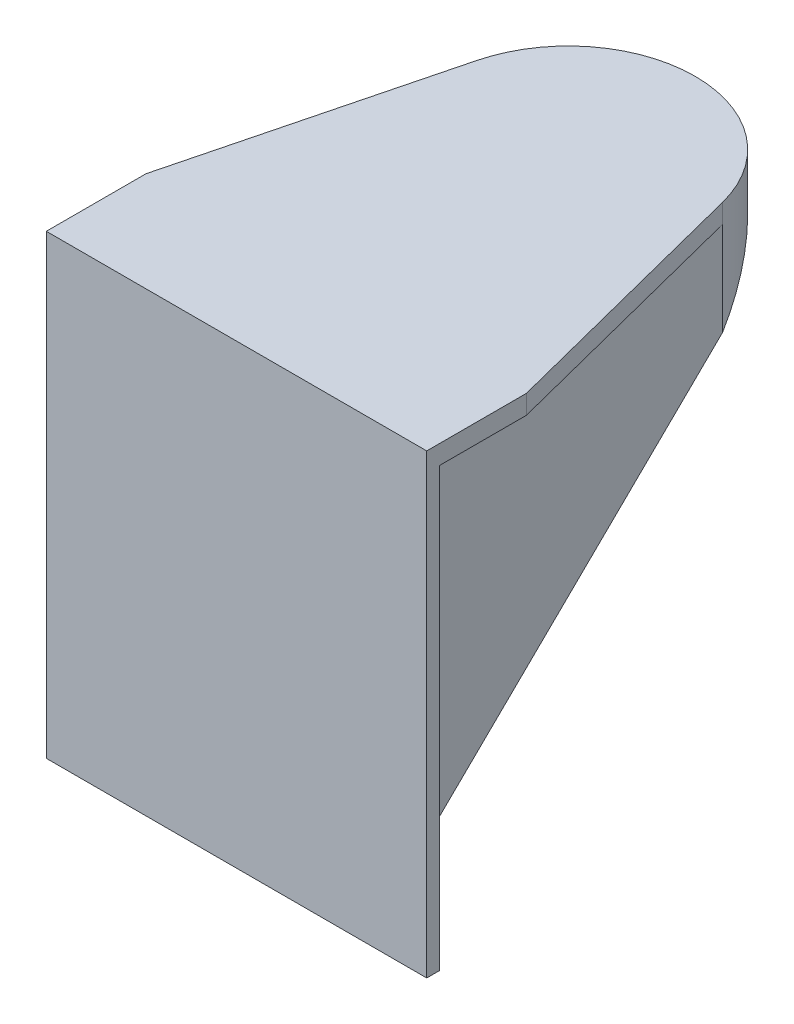
SolidWorks part; units mm, degrees
ref_plane "Front Plane" through (0, 0, 0) normal (0, 0, 1) x (1, 0, 0)
ref_plane "Top Plane" through (0, 0, 0) normal (0, 1, 0) x (1, 0, 0)
ref_plane "Right Plane" through (0, 0, 0) normal (1, 0, 0) x (0, 0, -1)
sketch "Sketch1" plane through (0, 0, 0) normal (0, 1, 0) x (1, 0, 0)
  line L0 (-30, -18) -> (30, -18) construction
  line L1 (-30, 10) -> (-22.5, 10) construction
  line L2 (-46.46, 5.4904) -> (-53.96, -7.5) construction
  line L3 (-30, -10) -> (-22.5, -10) construction
  line L4 (30, 10) -> (30, 2.5) construction
  line L5 (0, 0) -> (0, -75.5561) construction
  line L6 (38.6603, -23) -> (51.362, -45) construction
  line L7 (55.7735, -52.641) -> (58.3716, -51.141) construction
  line L8 (59.1036, -48.409) -> (41.8357, -18.5) construction
  line L9 (43.1036, -13.7679) -> (55.6921, -6.5) construction
  line L10 (56.4241, -3.7679) -> (51.362, 5) construction
  line L11 (25.3812, 20) -> (-25.3812, 20) construction
  line L12 (43.5677, -13.5) -> (36.0677, -0.5096) construction
  line L13 (36.0677, -0.5096) -> (46.46, 5.4904) construction
  line L14 (46.46, 5.4904) -> (53.96, -7.5) construction
  line L15 (-36.0677, -0.5096) -> (-46.46, 5.4904) construction
  line L16 (-43.5677, -13.5) -> (-36.0677, -0.5096) construction
  line L17 (-56.4241, -3.7679) -> (-51.362, 5) construction
  line L18 (-43.1036, -13.7679) -> (-55.6921, -6.5) construction
  line L19 (-59.1036, -48.409) -> (-41.8357, -18.5) construction
  line L20 (-55.7735, -52.641) -> (-58.3716, -51.141) construction
  line L21 (-38.6603, -23) -> (-51.362, -45) construction
  line L22 (-30, 10) -> (-30, 2.5) construction
  line L23 (30, 2.5) -> (25, 2.5) construction
  line L24 (25, 2.5) -> (25, -2.5) construction
  line L25 (25, -2.5) -> (30, -2.5) construction
  line L26 (30, -2.5) -> (30, -10) construction
  line L27 (22.5, -10) -> (22.5, -5) construction
  line L28 (22.5, -5) -> (17.5, -5) construction
  line L29 (17.5, -5) -> (17.5, -10) construction
  line L30 (22.5, -10) -> (30, -10) construction
  line L31 (17.5, 10) -> (17.5, 9) construction
  line L32 (17.5, 9) -> (22.5, 9) construction
  line L33 (22.5, 9) -> (22.5, 10) construction
  line L34 (22.5, 10) -> (30, 10) construction
  line L35 (2.5, -10) -> (2.5, -5) construction
  line L36 (2.5, -5) -> (-2.5, -5) construction
  line L37 (-2.5, -5) -> (-2.5, -10) construction
  line L38 (-2.5, 10) -> (-2.5, 9) construction
  line L39 (-2.5, 9) -> (2.5, 9) construction
  line L40 (2.5, 9) -> (2.5, 10) construction
  line L41 (-17.5, -10) -> (-17.5, -5) construction
  line L42 (-17.5, -5) -> (-22.5, -5) construction
  line L43 (-22.5, -5) -> (-22.5, -10) construction
  line L44 (-22.5, 10) -> (-22.5, 9) construction
  line L45 (-22.5, 9) -> (-17.5, 9) construction
  line L46 (-17.5, 9) -> (-17.5, 10) construction
  line L47 (-17.5, 10) -> (-2.5, 10) construction
  line L48 (-17.5, -10) -> (-2.5, -10) construction
  line L49 (2.5, -10) -> (17.5, -10) construction
  line L50 (2.5, 10) -> (17.5, 10) construction
  line L51 (-25, -2.5) -> (-30, -2.5) construction
  line L52 (-25, 2.5) -> (-25, -2.5) construction
  line L53 (-30, 2.5) -> (-25, 2.5) construction
  line L54 (-30, -2.5) -> (-30, -10) construction
  line L55 (-54.8261, -52) -> (54.8261, -52) construction
  line L56 (-49.6299, -48) -> (49.6299, -48) construction
  line L57 (-55.6921, -52.5) -> (-55.7735, -52.641) construction
  line L58 (55.6921, -52.5) -> (55.7735, -52.641) construction
  line L59 (207.8868, -326.1089) -> (177.8868, -378.0704) construction
  line L60 (232.1355, -340.1089) -> (228.3855, -346.6041) construction
  line L61 (214.815, -330.1089) -> (211.065, -336.6041) construction
  line L62 (202.1355, -392.0704) -> (195.6403, -388.3204) construction
  line L63 (169.2265, -383.0704) -> (143.8231, -383.0704) construction
  line L64 (135, -383.0704) -> (135, -386.0704) construction
  line L65 (137, -388.0704) -> (171.5359, -388.0704) construction
  line L66 (175, -391.5345) -> (175, -406.0704) construction
  line L67 (177, -408.0704) -> (187.1244, -408.0704) construction
  line L68 (213.1051, -393.0704) -> (238.4863, -349.1089) construction
  line L69 (233.4241, -310.3409) -> (238.4863, -319.1089) construction
  line L70 (218.1036, -316.8768) -> (230.6921, -309.6089) construction
  line L71 (196.1036, -285.6999) -> (213.3716, -315.6089) construction
  line L72 (190.7735, -286.4679) -> (193.3716, -284.9679) construction
  line L73 (207.8868, -316.1089) -> (195.185, -294.1089) construction
  line L74 (232.1355, -340.1089) -> (225.6403, -336.3589) construction
  line L75 (195.6403, -388.3204) -> (198.1403, -383.9903) construction
  line L76 (198.1403, -383.9903) -> (193.8101, -381.4903) construction
  line L77 (193.8101, -381.4903) -> (191.3101, -385.8204) construction
  line L78 (191.3101, -385.8204) -> (184.815, -382.0704) construction
  line L79 (188.565, -375.5752) -> (192.8951, -378.0752) construction
  line L80 (192.8951, -378.0752) -> (195.3951, -373.7451) construction
  line L81 (195.3951, -373.7451) -> (191.065, -371.2451) construction
  line L82 (188.565, -375.5752) -> (184.815, -382.0704) construction
  line L83 (208.3855, -381.2451) -> (207.5194, -380.7451) construction
  line L84 (207.5194, -380.7451) -> (205.0194, -385.0752) construction
  line L85 (205.0194, -385.0752) -> (205.8855, -385.5752) construction
  line L86 (205.8855, -385.5752) -> (202.1355, -392.0704) construction
  line L87 (198.565, -358.2547) -> (202.8951, -360.7547) construction
  line L88 (202.8951, -360.7547) -> (205.3951, -356.4246) construction
  line L89 (205.3951, -356.4246) -> (201.065, -353.9246) construction
  line L90 (218.3855, -363.9246) -> (217.5194, -363.4246) construction
  line L91 (217.5194, -363.4246) -> (215.0194, -367.7547) construction
  line L92 (215.0194, -367.7547) -> (215.8855, -368.2547) construction
  line L93 (208.565, -340.9342) -> (212.8951, -343.4342) construction
  line L94 (212.8951, -343.4342) -> (215.3951, -339.1041) construction
  line L95 (215.3951, -339.1041) -> (211.065, -336.6041) construction
  line L96 (228.3855, -346.6041) -> (227.5194, -346.1041) construction
  line L97 (227.5194, -346.1041) -> (225.0194, -350.4342) construction
  line L98 (225.0194, -350.4342) -> (225.8855, -350.9342) construction
  line L99 (225.8855, -350.9342) -> (218.3855, -363.9246) construction
  line L100 (208.565, -340.9342) -> (201.065, -353.9246) construction
  line L101 (198.565, -358.2547) -> (191.065, -371.2451) construction
  line L102 (215.8855, -368.2547) -> (208.3855, -381.2451) construction
  line L103 (218.8101, -338.189) -> (221.3101, -333.8589) construction
  line L104 (223.1403, -340.689) -> (218.8101, -338.189) construction
  line L105 (225.6403, -336.3589) -> (223.1403, -340.689) construction
  line L106 (221.3101, -333.8589) -> (214.815, -330.1089) construction
  line L107 (190.8549, -287.6089) -> (136.0289, -382.5704) construction
  line L108 (191.7209, -294.1089) -> (142.091, -380.0704) construction
  line L109 (190.8549, -286.6089) -> (190.7735, -286.4679) construction
  line L110 (135.1628, -383.0704) -> (135, -383.0704) construction
  line L111 (236.46, -323.5993) -> (228.96, -310.6089) construction
  line L112 (175, -392.0704) -> (190, -392.0704) construction
  line L113 (190, -392.0704) -> (190, -404.0704) construction
  line L114 (190, -404.0704) -> (175, -404.0704) construction
  line L115 (226.0677, -329.5993) -> (236.46, -323.5993) construction
  line L116 (218.5677, -316.6089) -> (226.0677, -329.5993) construction
  line L117 (-177.8868, -378.0704) -> (-207.8868, -326.1089) construction
  line L118 (-202.1355, -392.0704) -> (-205.8855, -385.5752) construction
  line L119 (-184.815, -382.0704) -> (-188.565, -375.5752) construction
  line L120 (-232.1355, -340.1089) -> (-225.6403, -336.3589) construction
  line L121 (-207.8868, -316.1089) -> (-195.185, -294.1089) construction
  line L122 (-190.7735, -286.4679) -> (-193.3716, -284.9679) construction
  line L123 (-196.1036, -285.6999) -> (-213.3716, -315.6089) construction
  line L124 (-218.1036, -316.8768) -> (-230.6921, -309.6089) construction
  line L125 (-233.4241, -310.3409) -> (-238.4863, -319.1089) construction
  line L126 (-238.4863, -349.1089) -> (-213.1051, -393.0704) construction
  line L127 (-177, -408.0704) -> (-187.1244, -408.0704) construction
  line L128 (-175, -391.5345) -> (-175, -406.0704) construction
  line L129 (-137, -388.0704) -> (-171.5359, -388.0704) construction
  line L130 (-135, -383.0704) -> (-135, -386.0704) construction
  line L131 (-169.2265, -383.0704) -> (-143.8231, -383.0704) construction
  line L132 (-202.1355, -392.0704) -> (-195.6403, -388.3204) construction
  line L133 (-225.6403, -336.3589) -> (-223.1403, -340.689) construction
  line L134 (-223.1403, -340.689) -> (-218.8101, -338.189) construction
  line L135 (-218.8101, -338.189) -> (-221.3101, -333.8589) construction
  line L136 (-221.3101, -333.8589) -> (-214.815, -330.1089) construction
  line L137 (-211.065, -336.6041) -> (-215.3951, -339.1041) construction
  line L138 (-215.3951, -339.1041) -> (-212.8951, -343.4342) construction
  line L139 (-212.8951, -343.4342) -> (-208.565, -340.9342) construction
  line L140 (-211.065, -336.6041) -> (-214.815, -330.1089) construction
  line L141 (-225.8855, -350.9342) -> (-225.0194, -350.4342) construction
  line L142 (-225.0194, -350.4342) -> (-227.5194, -346.1041) construction
  line L143 (-227.5194, -346.1041) -> (-228.3855, -346.6041) construction
  line L144 (-228.3855, -346.6041) -> (-232.1355, -340.1089) construction
  line L145 (-201.065, -353.9246) -> (-205.3951, -356.4246) construction
  line L146 (-205.3951, -356.4246) -> (-202.8951, -360.7547) construction
  line L147 (-202.8951, -360.7547) -> (-198.565, -358.2547) construction
  line L148 (-215.8855, -368.2547) -> (-215.0194, -367.7547) construction
  line L149 (-215.0194, -367.7547) -> (-217.5194, -363.4246) construction
  line L150 (-217.5194, -363.4246) -> (-218.3855, -363.9246) construction
  line L151 (-191.065, -371.2451) -> (-195.3951, -373.7451) construction
  line L152 (-195.3951, -373.7451) -> (-192.8951, -378.0752) construction
  line L153 (-192.8951, -378.0752) -> (-188.565, -375.5752) construction
  line L154 (-205.8855, -385.5752) -> (-205.0194, -385.0752) construction
  line L155 (-205.0194, -385.0752) -> (-207.5194, -380.7451) construction
  line L156 (-207.5194, -380.7451) -> (-208.3855, -381.2451) construction
  line L157 (-208.3855, -381.2451) -> (-215.8855, -368.2547) construction
  line L158 (-191.065, -371.2451) -> (-198.565, -358.2547) construction
  line L159 (-201.065, -353.9246) -> (-208.565, -340.9342) construction
  line L160 (-218.3855, -363.9246) -> (-225.8855, -350.9342) construction
  line L161 (-193.8101, -381.4903) -> (-191.3101, -385.8204) construction
  line L162 (-198.1403, -383.9903) -> (-193.8101, -381.4903) construction
  line L163 (-195.6403, -388.3204) -> (-198.1403, -383.9903) construction
  line L164 (-191.3101, -385.8204) -> (-184.815, -382.0704) construction
  line L165 (-136.0289, -382.5704) -> (-190.8549, -287.6089) construction
  line L166 (-142.091, -380.0704) -> (-191.7209, -294.1089) construction
  line L167 (-135.1628, -383.0704) -> (-135, -383.0704) construction
  line L168 (-190.8549, -286.6089) -> (-190.7735, -286.4679) construction
  line L169 (-190, -404.0704) -> (-175, -404.0704) construction
  line L170 (-218.5677, -316.6089) -> (-226.0677, -329.5993) construction
  line L171 (-226.0677, -329.5993) -> (-236.46, -323.5993) construction
  line L172 (-236.46, -323.5993) -> (-228.96, -310.6089) construction
  line L173 (-190, -392.0704) -> (-190, -404.0704) construction
  line L174 (-175, -392.0704) -> (-190, -392.0704) construction
  line L175 (-132.8534, -388.0704) -> (132.8534, -388.0704) construction
  line L176 (-132.8534, -388.0704) -> (-194.0303, -282.1089) construction
  line L177 (-194.0303, -282.1089) -> (-61.1769, -52) construction
  line L178 (-61.1769, -52) -> (61.1769, -52) construction
  line L179 (61.1769, -52) -> (194.0303, -282.1089) construction
  line L180 (-30, -408.0704) -> (30, -408.0704)
  line L181 (132.8534, -388.0704) -> (194.0303, -282.1089) construction
  line L182 (30, -372.3509) -> (30, -408.0704)
  line L183 (-30, -372.3509) -> (-30, -408.0704)
  line L184 (-21, -395.2107) -> (-21, -385.2107)
  line L185 (-25, -385.2107) -> (-25, -395.2107)
  line L186 (-30, -390.2107) -> (-25, -390.2107) construction
  line L187 (25, -385.2107) -> (25, -395.2107)
  line L188 (21, -395.2107) -> (21, -385.2107)
  circle A0 centre (0, 0) radius 31.6228 construction
  arc A1 (30, -18) -> (38.6603, -23) centre (30, -28) cw construction
  arc A2 (51.362, 5) -> (25.3812, 20) centre (25.3812, -10) ccw construction
  arc A3 (41.1036, -13.7679) -> (40.1036, -17.5) centre (40.1036, -15.5) ccw construction
  arc A4 (58.3716, -51.141) -> (59.1036, -48.409) centre (57.3716, -49.409) ccw construction
  arc A5 (55.6921, -6.5) -> (56.4241, -3.7679) centre (54.6921, -4.7679) ccw construction
  arc A6 (40.1036, -17.5) -> (41.8357, -18.5) centre (40.1036, -19.5) cw construction
  arc A7 (41.1036, -13.7679) -> (43.1036, -13.7679) centre (42.1036, -12.0359) ccw construction
  arc A8 (-41.1036, -13.7679) -> (-43.1036, -13.7679) centre (-42.1036, -12.0359) cw construction
  arc A9 (-40.1036, -17.5) -> (-41.8357, -18.5) centre (-40.1036, -19.5) ccw construction
  arc A10 (-55.6921, -6.5) -> (-56.4241, -3.7679) centre (-54.6921, -4.7679) cw construction
  arc A11 (-58.3716, -51.141) -> (-59.1036, -48.409) centre (-57.3716, -49.409) cw construction
  arc A12 (-41.1036, -13.7679) -> (-40.1036, -17.5) centre (-40.1036, -15.5) cw construction
  arc A13 (-51.362, 5) -> (-25.3812, 20) centre (-25.3812, -10) cw construction
  arc A14 (-30, -18) -> (-38.6603, -23) centre (-30, -28) ccw construction
  arc A15 (55.6921, -52.5) -> (54.8261, -52) centre (54.8261, -53) ccw construction
  arc A16 (-54.8261, -52) -> (-55.6921, -52.5) centre (-54.8261, -53) ccw construction
  arc A17 (49.6299, -48) -> (51.362, -45) centre (49.6299, -46) ccw construction
  arc A18 (-49.6299, -48) -> (-51.362, -45) centre (-49.6299, -46) cw construction
  circle A19 centre (0, -240.7264) radius 147.344 construction
  arc A20 (177.8868, -378.0704) -> (169.2265, -383.0704) centre (169.2265, -373.0704) cw construction
  arc A21 (187.1244, -408.0704) -> (213.1051, -393.0704) centre (187.1244, -378.0704) ccw construction
  arc A22 (176, -389.8025) -> (173.2679, -387.0704) centre (175, -388.0704) ccw construction
  arc A23 (135, -386.0704) -> (137, -388.0704) centre (137, -386.0704) ccw construction
  arc A24 (175, -406.0704) -> (177, -408.0704) centre (177, -406.0704) ccw construction
  arc A25 (173.2679, -387.0704) -> (171.5359, -388.0704) centre (171.5359, -386.0704) cw construction
  arc A26 (176, -389.8025) -> (175, -391.5345) centre (177, -391.5345) ccw construction
  arc A27 (217.1036, -318.6089) -> (218.1036, -316.8768) centre (219.1036, -318.6089) cw construction
  arc A28 (213.3716, -317.6089) -> (213.3716, -315.6089) centre (211.6395, -316.6089) ccw construction
  arc A29 (230.6921, -309.6089) -> (233.4241, -310.3409) centre (231.6921, -311.3409) cw construction
  arc A30 (193.3716, -284.9679) -> (196.1036, -285.6999) centre (194.3716, -286.6999) cw construction
  arc A31 (217.1036, -318.6089) -> (213.3716, -317.6089) centre (215.1036, -318.6089) cw construction
  arc A32 (238.4863, -319.1089) -> (238.4863, -349.1089) centre (212.5056, -334.1089) cw construction
  arc A33 (207.8868, -326.1089) -> (207.8868, -316.1089) centre (199.2265, -321.1089) ccw construction
  arc A34 (135.1628, -383.0704) -> (136.0289, -382.5704) centre (135.1628, -382.0704) ccw construction
  arc A35 (190.8549, -287.6089) -> (190.8549, -286.6089) centre (189.9889, -287.1089) ccw construction
  arc A36 (142.091, -380.0704) -> (143.8231, -383.0704) centre (143.8231, -381.0704) ccw construction
  arc A37 (191.7209, -294.1089) -> (195.185, -294.1089) centre (193.453, -295.1089) cw construction
  arc A38 (-207.8868, -326.1089) -> (-207.8868, -316.1089) centre (-199.2265, -321.1089) cw construction
  arc A39 (-238.4863, -319.1089) -> (-238.4863, -349.1089) centre (-212.5056, -334.1089) ccw construction
  arc A40 (-217.1036, -318.6089) -> (-213.3716, -317.6089) centre (-215.1036, -318.6089) ccw construction
  arc A41 (-193.3716, -284.9679) -> (-196.1036, -285.6999) centre (-194.3716, -286.6999) ccw construction
  arc A42 (-230.6921, -309.6089) -> (-233.4241, -310.3409) centre (-231.6921, -311.3409) ccw construction
  arc A43 (-213.3716, -317.6089) -> (-213.3716, -315.6089) centre (-211.6395, -316.6089) cw construction
  arc A44 (-217.1036, -318.6089) -> (-218.1036, -316.8768) centre (-219.1036, -318.6089) ccw construction
  arc A45 (-176, -389.8025) -> (-175, -391.5345) centre (-177, -391.5345) cw construction
  arc A46 (-173.2679, -387.0704) -> (-171.5359, -388.0704) centre (-171.5359, -386.0704) ccw construction
  arc A47 (-175, -406.0704) -> (-177, -408.0704) centre (-177, -406.0704) cw construction
  arc A48 (-135, -386.0704) -> (-137, -388.0704) centre (-137, -386.0704) cw construction
  arc A49 (-176, -389.8025) -> (-173.2679, -387.0704) centre (-175, -388.0704) cw construction
  arc A50 (-187.1244, -408.0704) -> (-213.1051, -393.0704) centre (-187.1244, -378.0704) cw construction
  arc A51 (-177.8868, -378.0704) -> (-169.2265, -383.0704) centre (-169.2265, -373.0704) ccw construction
  arc A52 (-190.8549, -286.6089) -> (-190.8549, -287.6089) centre (-189.9889, -287.1089) ccw construction
  arc A53 (-136.0289, -382.5704) -> (-135.1628, -383.0704) centre (-135.1628, -382.0704) ccw construction
  arc A54 (-191.7209, -294.1089) -> (-195.185, -294.1089) centre (-193.453, -295.1089) ccw construction
  arc A55 (-142.091, -380.0704) -> (-143.8231, -383.0704) centre (-143.8231, -381.0704) cw construction
  arc A56 (-30, -372.3509) -> (30, -372.3509) centre (0, -240.7264) ccw
  arc A57 (-21, -385.2107) -> (-25, -385.2107) centre (-23, -385.2107) ccw
  arc A58 (-25, -395.2107) -> (-21, -395.2107) centre (-23, -395.2107) ccw
  arc A59 (25, -395.2107) -> (21, -395.2107) centre (23, -395.2107) cw
  arc A60 (21, -385.2107) -> (25, -385.2107) centre (23, -385.2107) cw
  point P7 (-57.4241, -5.5)
  point P9 (0, -18)
  point P22 (35.7735, -18)
  point P27 (0, 10)
  point P30 (60.1036, -50.141)
  point P33 (57.4241, -5.5)
  point P61 (0, 20)
  point P65 (-60.1036, -50.141)
  point P66 (-35.7735, -18)
  point P104 (55.4034, -52)
  point P107 (-55.4034, -52)
  point P120 (232.4241, -308.6089)
  point P122 (192.8868, -352.0897)
  point P137 (217.1355, -366.0897)
  point P169 (225.7957, -371.0897)
  point P173 (195.1036, -283.9679)
  point P174 (210.7735, -321.1089)
  point P222 (-175, -408.0704)
  point P224 (-192.8868, -352.0897)
  point P239 (-217.1355, -366.0897)
  point P271 (-225.7957, -371.0897)
  point P275 (-135, -388.0704)
  point P276 (-175, -383.0704)
  point P320 (0, -240.7264)
  dimension "D12" = 10
  dimension "D14" = 30
  dimension "D16" = 2
  dimension "D17" = 2
  dimension "D28" = 1
  dimension "D29" = 2
  dimension "D31" = 270
  dimension "D35" = 2
  dimension "D2" = 30
  dimension "D3" = 5
  dimension "D4" = 8
  dimension "D5" = 40
  dimension "D6" = 20
  dimension "D7" = 350
  dimension "D8" = 10
  dimension "D9" = 4
  dimension "D10" = 12
  dimension "D11" = 15
  dimension "D13" = 20
  dimension "D15" = 34
  dimension "D18" = 5
  dimension "D19" = 2.5
  dimension "D20" = 5
  dimension "D21" = 5
  dimension "D22" = 5
  dimension "D23" = 7.5
  dimension "D24" = 1
  dimension "D26" = 20
  dimension "D27" = 4
  dimension "D32" = 60
  dimension "D33" = 30
  dimension "D34" = 5
  dimension "D36" = 10
  dimension "D25" = 3
  dimension "D30" = 3
extrude "Boss-Extrude1" add sketch "Sketch1" along normal blind 15
sketch "Sketch2" plane through (0, 0, 0) normal (0, 1, 0) x (1, 0, 0)
  line L0 (30, -372.3509) -> (19.3775, -330.7755)
  line L1 (-30, -372.3509) -> (-19.3775, -330.7755)
  line L2 (0, -375.7264) -> (0, -335.7264) construction
  arc A0 (19.3775, -330.7755) -> (-19.3775, -330.7755) centre (0, -335.7264) ccw
  arc A1 (-30, -372.3509) -> (30, -372.3509) centre (0, -240.7264) ccw construction
  arc A2 (-30, -372.3509) -> (30, -372.3509) centre (0, -240.7264) ccw
  dimension "D2" = 20
  dimension "D1" = 40
extrude "Boss-Extrude2" add sketch "Sketch2" along normal blind 10
sketch "Sketch3" plane through (0, 10, 0) normal (0, 1, 0) x (1, 0, 0)
  circle A0 centre (0, -335.7264) radius 3.25
  arc A1 (19.3775, -330.7755) -> (-19.3775, -330.7755) centre (0, -335.7264) ccw construction
  dimension "D1" = 6.5
extrude "Cut-Extrude1" cut sketch "Sketch3" against normal offset from surface (9 mm away) 1 contours A0 up to face at (-23, 0, 390.2107)
sketch "Sketch4" plane through (0, 10, 0) normal (0, 1, 0) x (1, 0, 0)
  line L0 (30, -372.3509) -> (19.3775, -330.7755)
  line L1 (-30, -372.3509) -> (-19.3775, -330.7755)
  circle A0 centre (0, -335.7264) radius 6
  arc A1 (19.3775, -330.7755) -> (-19.3775, -330.7755) centre (0, -335.7264) ccw
  arc A2 (-30, -372.3509) -> (30, -372.3509) centre (0, -240.7264) ccw
  arc A3 (-30, -372.3509) -> (30, -372.3509) centre (0, -240.7264) ccw construction
  dimension "D1" = 12
extrude "Cut-Extrude2" cut sketch "Sketch4" against normal offset from surface (7 mm away) 3 up to face at (-23, 0, 390.2107)
chamfer "Chamfer1" distance 10 distance2 20 1 edges at (0, 3, 341.7264) first distance on face at (0, 3, 341.7264)
chamfer "Chamfer2" distance 5 distance2 3 1 edges at (0, 10, 338.9764) first distance on face at (0, 10, 347.7264)
sketch "Sketch5" plane through (0, 15, 0) normal (0, 1, 0) x (1, 0, 0)
  line L0 (-30, -408.0704) -> (30, -408.0704) construction
  line L1 (-11, -408.0704) -> (11, -408.0704)
  line L2 (-11, -408.0704) -> (-11, -375.2775)
  line L3 (-11, -375.2775) -> (11, -375.2775)
  line L4 (11, -408.0704) -> (11, -375.2775)
  line L5 (-21, -395.2107) -> (-21, -385.2107) construction
  line L6 (21, -385.2107) -> (21, -395.2107) construction
  arc A0 (-30, -372.3509) -> (30, -372.3509) centre (0, -240.7264) ccw construction
  dimension "D1" = 10
  dimension "D2" = 10
extrude "Cut-Extrude3" cut sketch "Sketch5" against normal up to surface (12 mm away) up to face at (0, 3, 364.1689)
fillet "Fillet1" radius 10 2 edges at (-11, 9, 375.2775) (11, 9, 375.2775)
fillet "Fillet2" radius 10 2 edges at (30, 7.5, 408.0704) (-30, 7.5, 408.0704)
sketch "Sketch6" plane through (0, 0, 0) normal (0, -1, 0) x (1, 0, 0)
  line L0 (-30, 372.3509) -> (-30, 398.0704) construction
  line L1 (-30, 388.0704) -> (30, 388.0704)
  line L2 (-30, 388.0704) -> (-30, 372.3509)
  line L3 (-20, 408.0704) -> (20, 408.0704) construction
  line L4 (30, 388.0704) -> (30, 372.3509)
  line L5 (30, 372.3509) -> (19.3775, 330.7755)
  line L6 (-30, 372.3509) -> (-19.3775, 330.7755)
  arc A0 (-19.3775, 330.7755) -> (19.3775, 330.7755) centre (0, 335.7264) ccw
  arc A1 (-19.3775, 330.7755) -> (19.3775, 330.7755) centre (0, 335.7264) ccw construction
  dimension "D1" = 20
extrude "Boss-Extrude3" add sketch "Sketch6" along normal blind 3
sketch "Sketch7" plane through (0, -3, 0) normal (0, -1, 0) x (1, 0, 0)
  line L0 (30, 372.3509) -> (30, 388.0704) construction
  line L1 (-30, 388.0704) -> (30, 388.0704)
  line L2 (-30, 388.0704) -> (-30, 386.0704)
  line L3 (-30, 386.0704) -> (30, 386.0704)
  line L4 (30, 388.0704) -> (30, 386.0704)
  dimension "D1" = 2
extrude "Boss-Extrude4" add sketch "Sketch7" along normal blind 69
sketch "Sketch8" plane through (0, 0, 0) normal (0, 1, 0) x (1, 0, 0)
  line L0 (11, -408.0704) -> (-11, -408.0704) construction
  line L1 (-30, -408.0704) -> (30, -408.0704)
  line L2 (-30, -408.0704) -> (-30, -315.7264)
  line L3 (-30, -315.7264) -> (30, -315.7264)
  line L4 (30, -408.0704) -> (30, -315.7264)
  line L5 (-30, -372.3509) -> (-30, -398.0704) construction
  line L6 (30, -398.0704) -> (30, -372.3509) construction
  arc A0 (19.3775, -330.7755) -> (-19.3775, -330.7755) centre (0, -335.7264) ccw construction
extrude "Cut-Extrude4" cut sketch "Sketch8" along normal through all
sketch "Sketch9" plane through (0, -3, 0) normal (0, -1, 0) x (1, 0, 0)
  line L0 (-30, 386.0704) -> (30, 386.0704) construction
  line L1 (-2.5, 386.0704) -> (2.5, 386.0704)
  line L2 (-2.5, 386.0704) -> (-2.5, 315.8833)
  line L3 (-30, 386.0704) -> (30, 386.0704) construction
  line L4 (2.5, 386.0704) -> (2.5, 315.8833)
  line L5 (14.3775, 386.0704) -> (19.3775, 386.0704)
  line L6 (14.3775, 386.0704) -> (14.3775, 321.8237)
  line L7 (0, 335.7264) -> (0, 50335.7264) construction
  line L8 (19.3775, 386.0704) -> (19.3775, 330.7755)
  line L9 (-19.3775, 386.0704) -> (-19.3775, 330.7755)
  line L10 (-14.3775, 386.0704) -> (-14.3775, 321.8237)
  line L11 (-14.3775, 386.0704) -> (-19.3775, 386.0704)
  arc A0 (-19.3775, 330.7755) -> (-14.3775, 321.8237) centre (0, 335.7264) ccw
  arc A1 (-19.3775, 330.7755) -> (19.3775, 330.7755) centre (0, 335.7264) ccw construction
  arc A2 (14.3775, 321.8237) -> (19.3775, 330.7755) centre (0, 335.7264) ccw
  arc A3 (-2.5, 315.8833) -> (2.5, 315.8833) centre (0, 335.7264) ccw
  dimension "D1" = 5
  dimension "D2" = 2.5
  dimension "D3" = 5
extrude "Boss-Extrude5" add sketch "Sketch9" along normal up to surface (69 mm away) up to face at (0, -72, 387.0704)
sketch "Sketch10" plane through (0, 0, 0) normal (1, 0, 0) x (0, 0, -1)
  line L0 (-386.0704, -72) -> (-315.7264, -72)
  line L1 (-315.7264, -72) -> (-315.7264, -3)
  line L2 (-315.7264, -3) -> (-386.0704, -72)
  line L3 (-315.7264, -72) -> (-315.7264, 0) construction
  line L4 (-315.8833, -3) -> (-386.0704, -3) construction
extrude "Cut-Extrude5" cut sketch "Sketch10" against normal through all and the other way through all
